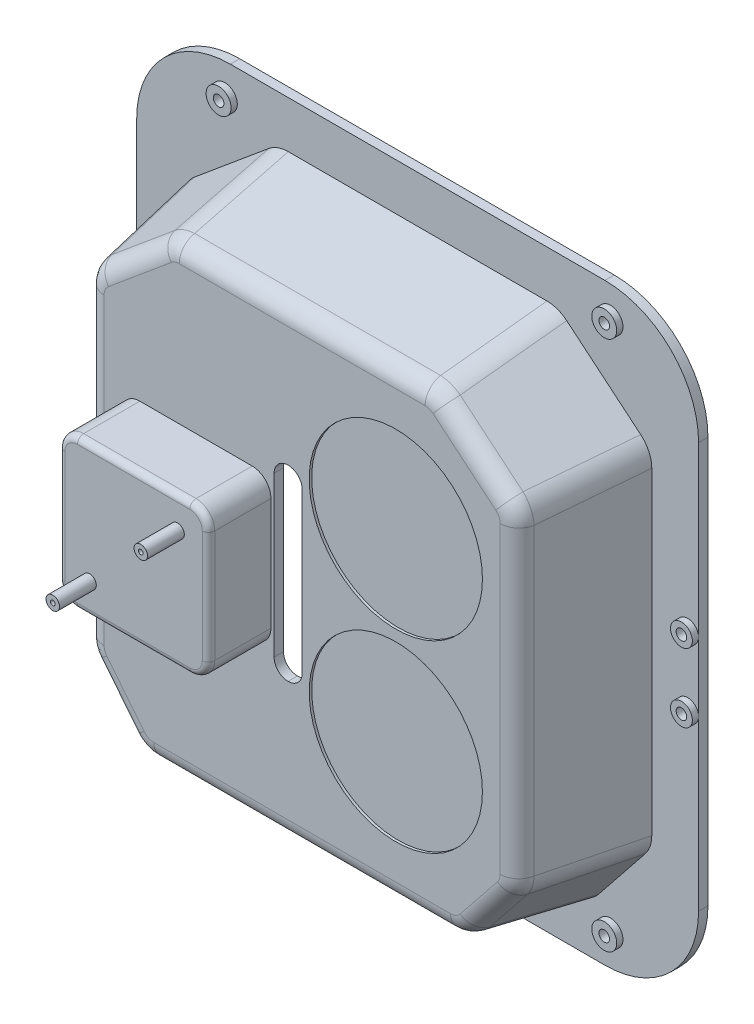
SolidWorks part; units mm, degrees
ref_plane "Front Plane" through (0, 0, 0) normal (0, 0, 1) x (1, 0, 0)
ref_plane "Top Plane" through (0, 0, 0) normal (0, 1, 0) x (1, 0, 0)
ref_plane "Right Plane" through (0, 0, 0) normal (1, 0, 0) x (0, 0, -1)
sketch "SK_Brim_180x190" plane through (0, 0, 0) normal (0, 0, 1) x (1, 0, 0)
  line L1 (-90, -95) -> (90, -95)
  line L2 (-90, -95) -> (-90, 95)
  line L3 (-90, 95) -> (90, 95)
  line L4 (90, -95) -> (90, 95)
  line L5 (-72, -77) -> (72, -77)
  line L6 (-72, -77) -> (-72, 77)
  line L7 (-72, 77) -> (72, 77)
  line L8 (72, -77) -> (72, 77)
extrude "Board_Mount_Brim_3mm" add sketch "SK_Brim_180x190" along normal blind 3
fillet "Brim_Outer_R30" radius 30 4 edges at (-90, 95, 1.5) (90, 95, 1.5) (90, -95, 1.5) (-90, -95, 1.5)
fillet "Brim_Inner_R10" radius 10 4 edges at (-72, 77, 1.5) (72, 77, 1.5) (72, -77, 1.5) (-72, -77, 1.5)
sketch "SK_Cockpit_Octagon" plane through (0, 0, 3) normal (0, 0, 1) x (1, 0, 0)
  line L0 (-55, -80) -> (55, -80)
  line L1 (55, -80) -> (75, -55)
  line L2 (75, -55) -> (75, 55)
  line L3 (75, 55) -> (45, 80)
  line L4 (45, 80) -> (-45, 80)
  line L5 (-45, 80) -> (-75, 55)
  line L6 (-75, 55) -> (-75, -55)
  line L7 (-75, -55) -> (-55, -80)
extrude "Cockpit_Canopy_37H_Draft10deg" add sketch "SK_Cockpit_Octagon" along normal blind 37 draft 10
fillet "Canopy_Corners_R10" radius 10 8 edges at (-71.738, -53.8557, 21.5) (-71.738, 53.4721, 21.5) (-43.819, 76.738, 21.5) (43.819, 76.738, 21.5) (71.738, 53.4721, 21.5) (71.738, -53.8557, 21.5) (53.4322, -76.738, 21.5) (-53.4322, -76.738, 21.5)
fillet "Canopy_Roof_R6" radius 6 16 edges at (-60.5695, -62.5944, 40) (0, -73.4759, 40) (60.5695, -62.5944, 40) (68.4759, -0.9626, 40) (55.1547, 63.0453, 40) (0, 73.4759, 40) (-55.1547, 63.0453, 40) (-68.4759, -0.9626, 40) (-51.398, -72.5055, 40) (51.398, -72.5055, 40) (67.9212, -52.5169, 40) (67.5476, 51.5095, 40) (42.4252, 72.8883, 40) (-42.4252, 72.8883, 40) (-67.5476, 51.5095, 40) (-67.9212, -52.5169, 40)
sketch "SK_Symmetric_Cavity" plane through (0, 0, 0) normal (0, 0, -1) x (-1, 0, 0)
  line L0 (-53, -77) -> (53, -77)
  line L1 (57.3444, -77) -> (-57.3444, -77) construction
  line L2 (53, -77) -> (72, -52)
  line L3 (72, 57.4649) -> (72, -58.75) construction
  line L4 (72, -52) -> (72, 52)
  line L5 (72, 52) -> (43, 77)
  line L6 (-62, 77) -> (62, 77) construction
  line L7 (43, 77) -> (-43, 77)
  line L8 (-43, 77) -> (-72, 52)
  line L9 (-72, -67) -> (-72, 67) construction
  line L10 (-72, 52) -> (-72, -52)
  line L11 (-72, -52) -> (-53, -77)
extrude "Symmetric_Electronics_Cavity_37H" cut sketch "SK_Symmetric_Cavity" against normal blind 37 draft 10
sketch "Sketch14" plane through (0, 0, 40) normal (0, 0, 1) x (1, 0, 0)
  line L1 (-58, -24) -> (-10, -24)
  line L2 (-58, -24) -> (-58, 24)
  line L3 (-58, 24) -> (-10, 24)
  line L4 (-10, -24) -> (-10, 24)
extrude "LD06_Raised_Base_20H" add sketch "Sketch14" along normal blind 20
fillet "Fillet3" radius 6 4 edges at (-58, 24, 50) (-10, 24, 50) (-10, -24, 50) (-58, -24, 50)
fillet "Fillet4" radius 2 8 edges at (-58, 0, 60) (-34, -24, 60) (-10, 0, 60) (-34, 24, 60) (-56.2426, -22.2426, 60) (-11.7574, -22.2426, 60) (-11.7574, 22.2426, 60) (-56.2426, 22.2426, 60)
sketch "Sketch15" plane through (0, 0, 60) normal (0, 0, 1) x (1, 0, 0)
  circle A0 centre (-48.1, -14.1) radius 2.15
  circle A1 centre (-19.9, 14.1) radius 2.15
extrude "Boss-Extrude6" add sketch "Sketch15" along normal blind 11.8
sketch "Sketch16" plane through (0, 0, 71.8) normal (0, 0, 1) x (1, 0, 0)
  circle A0 centre (-48.1, -14.1) radius 0.75
  circle A1 centre (-19.9, 14.1) radius 0.75
extrude "Cut-Extrude10" cut sketch "Sketch16" against normal blind 11.3
sketch "Sketch19" plane through (0, 0, 0) normal (0, 0, 1) x (1, 0, 0)
  line L0 (-50, -73) -> (50, -73)
  line L1 (-72, -77) -> (72, -77)
  line L2 (-72, -77) -> (-72, 77)
  line L3 (-72, 77) -> (72, 77)
  line L4 (72, -77) -> (72, 77)
  line L5 (50, -73) -> (68, -50)
  line L6 (68, -50) -> (68, 50)
  line L7 (68, 50) -> (40, 73)
  line L8 (40, 73) -> (-40, 73)
  line L9 (-40, 73) -> (-68, 50)
  line L10 (-68, 50) -> (-68, -50)
  line L11 (-68, -50) -> (-50, -73)
extrude "Boss-Extrude7" add sketch "Sketch19" along normal blind 3
sketch "Sketch20" plane through (0, 0, 3) normal (0, 0, 1) x (1, 0, 0)
  circle A0 centre (-86.5, -11) radius 1.7
  circle A1 centre (-86.5, 11) radius 1.7
  circle A2 centre (86.5, -11) radius 1.7
  circle A3 centre (86.5, 11) radius 1.7
  circle A4 centre (-61.7761, -84.9997) radius 1.7
  circle A5 centre (61.7761, -84.9997) radius 1.7
  circle A6 centre (-61.7761, 84.9997) radius 1.7
  circle A7 centre (61.7761, 84.9997) radius 1.7
extrude "Cut-Extrude13" cut sketch "Sketch20" against normal blind 3.2
sketch "Sketch21" plane through (0, 0, 40) normal (0, 0, 1) x (1, 0, 0)
  circle A0 centre (30, -29.5) radius 27.75
extrude "Cut-Extrude14" cut sketch "Sketch21" against normal blind 0.8
sketch "Sketch22" plane through (0, 0, 40) normal (0, 0, 1) x (1, 0, 0)
  circle A0 centre (30, 29.5) radius 27.75
extrude "Cut-Extrude15" cut sketch "Sketch22" against normal blind 0.8
sketch "Sketch24" plane through (0, 0, 40) normal (0, 0, 1) x (1, 0, 0)
  line L1 (-9, -30) -> (0, -30)
  line L2 (-9, -30) -> (-9, 30)
  line L3 (-9, 30) -> (0, 30)
  line L4 (0, -30) -> (0, 30)
extrude "Cut-Extrude18" cut sketch "Sketch24" against normal blind 4
fillet "Fillet5" radius 4.5 4 edges at (-9, -30, 38.5) (0, -30, 38.5) (0, 30, 38.5) (-9, 30, 38.5)
sketch "Sketch25" plane through (0, 0, 3) normal (0, 0, 1) x (1, 0, 0)
  circle A0 centre (-86.5, -11) radius 4
  circle A1 centre (-86.5, -11) radius 1.7
  circle A2 centre (-86.5, 11) radius 4
  circle A3 centre (-86.5, 11) radius 1.7
  circle A4 centre (86.5, -11) radius 3.5
  circle A5 centre (86.5, -11) radius 1.7
  circle A6 centre (86.5, 11) radius 3.5
  circle A7 centre (86.5, 11) radius 1.7
  circle A8 centre (-61.7761, -84.9997) radius 4
  circle A9 centre (-61.7761, -84.9997) radius 1.7
  circle A10 centre (61.7761, -84.9997) radius 4
  circle A11 centre (61.7761, -84.9997) radius 1.7
  circle A12 centre (-61.7761, 84.9997) radius 4
  circle A13 centre (-61.7761, 84.9997) radius 1.7
  circle A14 centre (61.7761, 84.9997) radius 4
  circle A15 centre (61.7761, 84.9997) radius 1.7
extrude "Boss-Extrude8" add sketch "Sketch25" along normal blind 2
sketch "SK_LD06_Single_Pocket_With_Support_Islands" plane through (0, 0, 37) normal (0, 0, -1) x (-1, 0, 0)
  line L1 (12, -22) -> (56, -22)
  line L2 (12, -22) -> (12, 22)
  line L3 (12, 22) -> (56, 22)
  line L4 (56, -22) -> (56, 22)
  circle A0 centre (48.1, -14.1) radius 5.5
  circle A1 centre (19.9, 14.1) radius 5.5
extrude "LD06_Single_Hollow_Pedestal_Pocket" cut sketch "SK_LD06_Single_Pocket_With_Support_Islands" against normal blind 20
